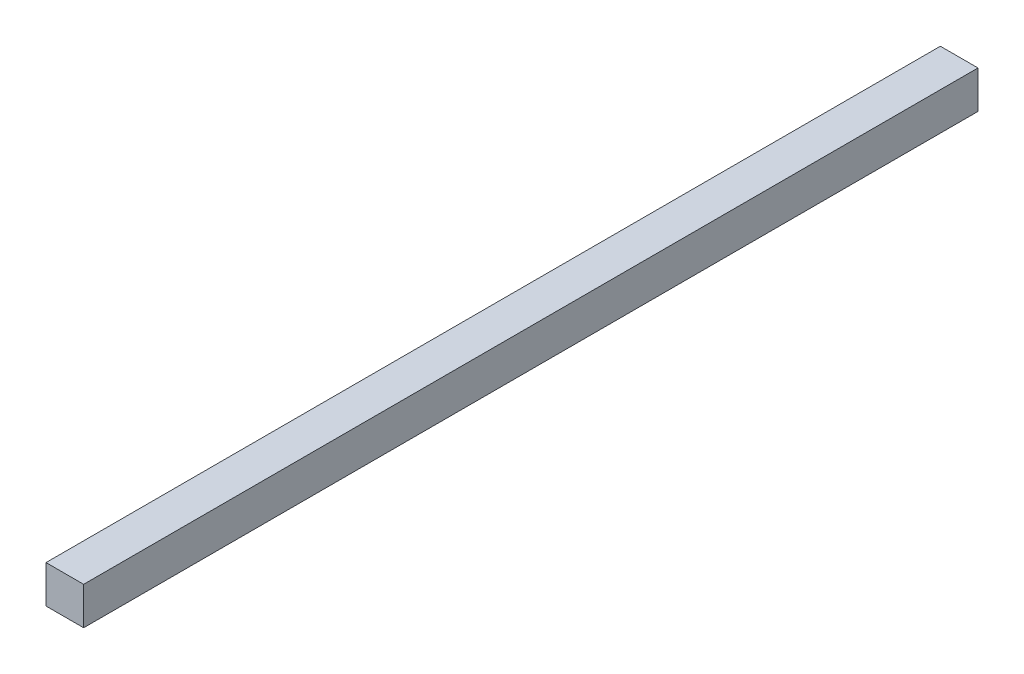
SolidWorks part; units mm, degrees
ref_plane "Front Plane" through (0, 0, 0) normal (0, 0, 1) x (1, 0, 0)
ref_plane "Top Plane" through (0, 0, 0) normal (0, 1, 0) x (1, 0, 0)
ref_plane "Right Plane" through (0, 0, 0) normal (1, 0, 0) x (0, 0, -1)
sketch "Sketch2" plane through (0, 0, 0) normal (0, 0, 1) x (1, 0, 0)
  circle A0 centre (0, 0) radius 1.25
  dimension "D1" = 2.5
sketch "Sketch3" plane through (0, 0, 0) normal (0, 0, 1) x (1, 0, 0)
  line L5 (-2, 2) -> (2, 2)
  line L6 (-2, 2) -> (-2, -2)
  line L7 (-2, -2) -> (2, -2)
  line L8 (2, 2) -> (2, -2)
  point P4 (0, 2)
  point P6 (-2, 0)
  dimension "D1" = 4
extrude "Boss-Extrude1" add sketch "Sketch3" along normal blind 95
